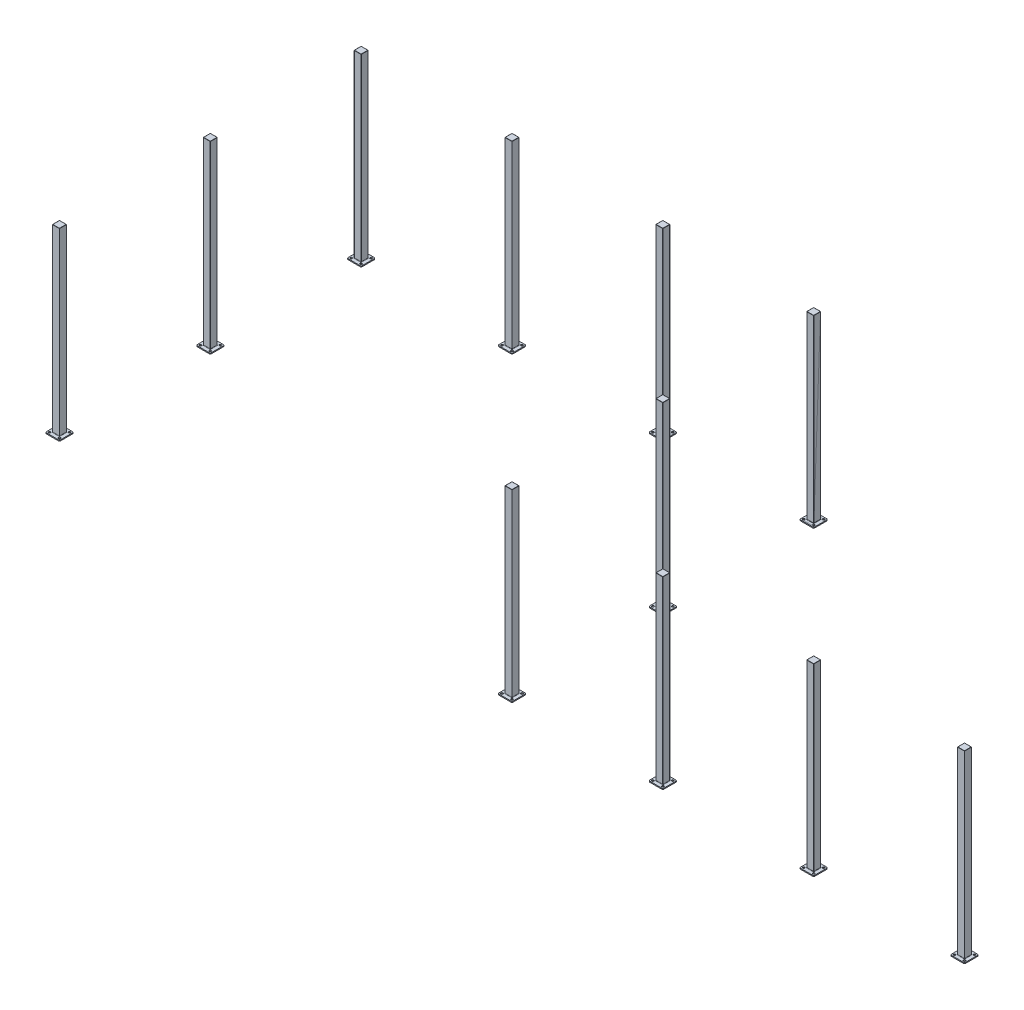
SolidWorks part; units mm, degrees
ref_plane "Front Plane" through (0, 0, 0) normal (0, 0, 1) x (1, 0, 0)
ref_plane "Top Plane" through (0, 0, 0) normal (0, 1, 0) x (1, 0, 0)
ref_plane "Right Plane" through (0, 0, 0) normal (1, 0, 0) x (0, 0, -1)
sketch "Sketch1" plane through (0, 0, 0) normal (0, 1, 0) x (1, 0, 0)
  line L1 (-2250, 0) -> (-2250, 3000)
  line L2 (-2250, 3000) -> (2250, 3000)
  line L3 (2250, 3000) -> (2250, 0)
  line L4 (2250, 0) -> (5450, 0)
  line L5 (0, 0) -> (0, 3000) construction
  point P0 (0, 0)
  point P9 (0, 0)
  dimension "D1" = 4500
  dimension "D2" = 3000
  dimension "D3" = 3200
ref_plane "Plane1" through (-2250, 0, 0) normal (1, 0, 0) x (0, 0, -1)
sketch "Sketch2" plane through (-2250, 0, 0) normal (1, 0, 0) x (0, 0, -1)
  line L1 (35, 1800) -> (-35, 1800)
  line L2 (35, 1800) -> (35, 0)
  line L3 (35, 0) -> (-35, 0)
  line L4 (-35, 1800) -> (-35, 0)
  line L5 (35, 1800) -> (-35, 0) construction
  line L6 (35, 0) -> (-35, 1800) construction
  point P0 (0, 900)
  point P5 (0, 0)
  point P6 (0, 0)
  dimension "D1" = 1800
  dimension "D2" = 70
extrude "Boss-Extrude1" add sketch "Sketch2" along normal mid plane 70
sketch "Sketch3" plane through (0, 0, 0) normal (0, -1, 0) x (1, 0, 0)
  line L1 (-2320, 70) -> (-2180, 70)
  line L2 (-2320, 70) -> (-2320, -70)
  line L3 (-2320, -70) -> (-2180, -70)
  line L4 (-2180, 70) -> (-2180, -70)
  line L5 (-2320, 70) -> (-2180, -70) construction
  line L6 (-2320, -70) -> (-2180, 70) construction
  circle A0 centre (-2200.5025, 49.4975) radius 10
  circle A1 centre (-2200.5025, -49.4975) radius 10
  circle A2 centre (-2299.4975, -49.4975) radius 10
  circle A3 centre (-2299.4975, 49.4975) radius 10
  point P0 (-2250, 0)
  point P8 (0, 0)
  point P17 (-2250, 0)
  dimension "D2" = 4
  dimension "D4" = 20
  dimension "D1" = 140
  dimension "D3" = 70
extrude "Boss-Extrude2" add sketch "Sketch3" against normal blind 10
fillet "Fillet1" radius 10 4 edges at (-2180, 5, -70) (-2180, 5, 70) (-2320, 5, -70) (-2320, 5, 70)
fillet "Fillet2" radius 2 8 edges at (-2250, 1800, -35) (-2215, 1800, 0) (-2250, 1800, 35) (-2285, 1800, 0) (-2285, 905, 35) (-2215, 905, 35) (-2215, 905, -35) (-2285, 905, -35)
fillet "Fillet3" radius 3 8 edges at (-2215.5858, 10, 34.4142) (-2215, 10, 0) (-2215.5858, 10, -34.4142) (-2250, 10, -35) (-2284.4142, 10, -34.4142) (-2285, 10, 0) (-2284.4142, 10, 34.4142) (-2250, 10, 35)
pattern_linear "LPattern1" count 3 spacing 1500 along (0, 0, -1) of bodies 102
pattern_linear "LPattern2" count 4 spacing 1500 along (1, 0, 0) of bodies 105
mirror "Mirror1" about plane through (0, 0, 0) normal (1, 0, 0) of bodies 104 105 102 109
pattern_linear "LPattern3" count 4 spacing 1500 along (1, 0, 0) of bodies 115
